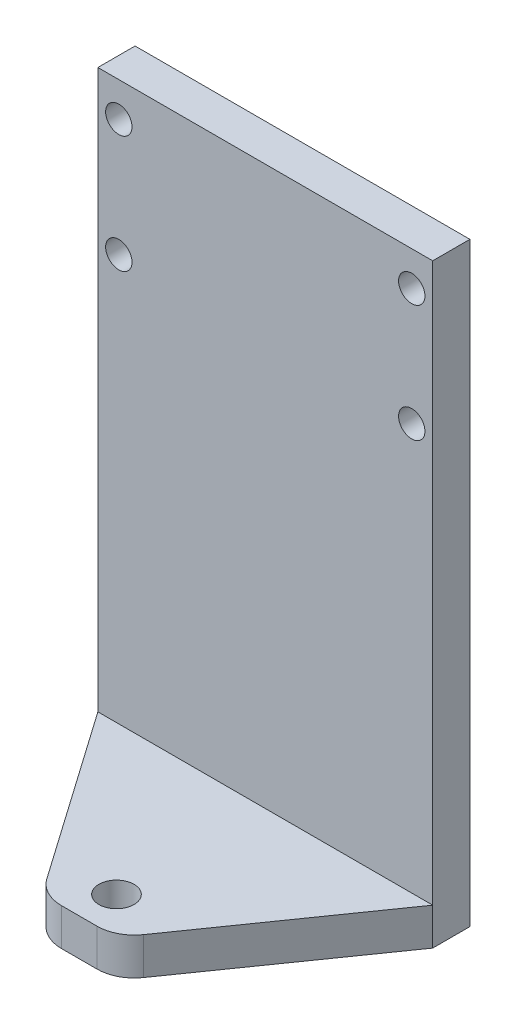
SolidWorks part; units mm, degrees
material "PLA White"
ref_plane "Front" through (0, 0, 0) normal (0, 0, 1) x (1, 0, 0)
ref_plane "Top" through (0, 0, 0) normal (0, 1, 0) x (1, 0, 0)
ref_plane "Right" through (0, 0, 0) normal (1, 0, 0) x (0, 0, -1)
sketch "Sketch1" plane through (0, 0, 0) normal (0, 0, 1) x (1, 0, 0)
  line L1 (-28.575, -50.8) -> (28.575, -50.8)
  line L2 (-28.575, -50.8) -> (-28.575, 50.8)
  line L3 (-28.575, 50.8) -> (28.575, 50.8)
  line L4 (28.575, -50.8) -> (28.575, 50.8)
  line L5 (-28.575, -50.8) -> (28.575, 50.8) construction
  line L6 (-28.575, 50.8) -> (28.575, -50.8) construction
  point P0 (0, 0)
  dimension "D1" = 57.15
  dimension "D2" = 101.6
extrude "Boss-Extrude1" add sketch "Sketch1" along normal mid plane 6.35
sketch "Sketch2" plane through (0, -50.8, 0) normal (0, -1, 0) x (1, 0, 0)
  line L0 (-28.575, 3.175) -> (28.575, 3.175) construction
  line L1 (-28.575, -3.175) -> (28.575, -3.175)
  line L2 (-28.575, -3.175) -> (-28.575, 53.975)
  line L3 (-28.575, 53.975) -> (28.575, 53.975)
  line L4 (28.575, -3.175) -> (28.575, 53.975)
  dimension "D1" = 50.8
extrude "Boss-Extrude2" add sketch "Sketch2" against normal blind 6.35
sketch "Sketch3" plane through (0, 0, -3.175) normal (0, 0, -1) x (-1, 0, 0)
  circle A0 centre (-25, 44.925) radius 2.25 construction
  circle A1 centre (-25, 24.925) radius 2.25 construction
  circle A2 centre (25, 24.925) radius 2.25 construction
  circle A3 centre (25, 44.925) radius 2.25 construction
  circle A4 centre (-25, 44.925) radius 2.25
  circle A5 centre (-25, 24.925) radius 2.25
  circle A6 centre (25, 24.925) radius 2.25
  circle A7 centre (25, 44.925) radius 2.25
extrude "Cut-Extrude1" cut sketch "Sketch3" against normal through all
sketch "Sketch4" plane through (0, -44.45, 0) normal (0, 1, 0) x (1, 0, 0)
  line L0 (-28.575, -53.975) -> (-28.575, -3.175) construction
  line L1 (28.575, -53.975) -> (-28.575, -53.975) construction
  circle A0 centre (0, -28.575) radius 3
  point P4 (-28.575, -28.575)
  point P7 (0, -53.975)
  dimension "D1" = 6
extrude "Cut-Extrude2" cut sketch "Sketch4" against normal through all
sketch "Sketch5" plane through (0, -44.45, 0) normal (0, 1, 0) x (1, 0, 0)
  line L0 (-28.575, -3.175) -> (-6.35, -34.925)
  line L1 (-6.35, -34.925) -> (6.35, -34.925)
  line L2 (6.35, -34.925) -> (28.575, -3.175)
  line L3 (28.575, -3.175) -> (28.575, -53.975)
  line L4 (28.575, -53.975) -> (-28.575, -53.975)
  line L5 (-28.575, -53.975) -> (-28.575, -3.175)
  line L6 (0, -34.925) -> (0, -53.975) construction
  circle A0 centre (0, -28.575) radius 3 construction
  dimension "D1" = 6.35
  dimension "D2" = 12.7
extrude "Cut-Extrude3" cut sketch "Sketch5" against normal through all
fillet "Fillet1" radius 6.35 2 edges at (6.35, -47.625, 34.925) (-6.35, -47.625, 34.925)
